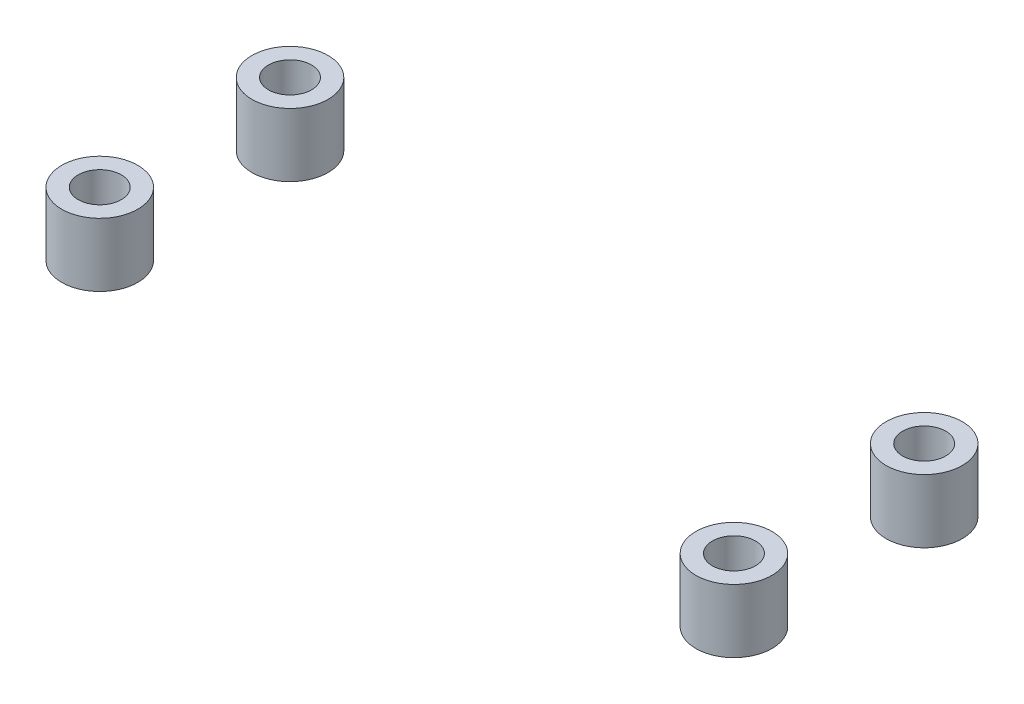
SolidWorks part; units mm, degrees
ref_plane "Front Plane" through (0, 0, 0) normal (0, 0, 1) x (1, 0, 0)
ref_plane "Top Plane" through (0, 0, 0) normal (0, 1, 0) x (1, 0, 0)
ref_plane "Right Plane" through (0, 0, 0) normal (1, 0, 0) x (0, 0, -1)
sketch "Sketch1" plane through (0, 0, 0) normal (0, 1, 0) x (1, 0, 0)
  line L0 (-15.6, 17.4701) -> (-13.6201, 19.45) construction
  line L1 (-13.6201, 19.45) -> (13.6201, 19.45) construction
  line L2 (-15.6, 17.4701) -> (-15.6, -19.45) construction
  line L3 (-15.6, -19.45) -> (15.6, -19.45) construction
  line L4 (15.6, 17.4701) -> (15.6, -19.45) construction
  line L5 (-14.7188, 18.3513) -> (15.6, -19.45) construction
  line L6 (-15.6, -19.45) -> (14.7188, 18.3513) construction
  line L7 (-13.6201, 19.45) -> (13.6201, 19.45) construction
  line L8 (13.6201, 19.45) -> (15.6, 17.4701) construction
  point P0 (0, 0)
  dimension "D1" = 31.2
  dimension "D2" = 38.9
  dimension "D3" = 45
  dimension "D4" = 2.8
  dimension "D5" = 2.8
  dimension "D6" = 19.45
  dimension "D7" = 15.6
sketch "Sketch2" plane through (0, 0, 0) normal (0, 1, 0) x (1, 0, 0)
  line L1 (-25, 7.5) -> (25, 7.5) construction
  line L2 (-25, 7.5) -> (-25, -7.5) construction
  line L3 (-25, -7.5) -> (25, -7.5) construction
  line L4 (25, 7.5) -> (25, -7.5) construction
  line L5 (-25, 7.5) -> (25, -7.5) construction
  line L6 (-25, -7.5) -> (25, 7.5) construction
  circle A0 centre (-25, 7.5) radius 1.7
  circle A1 centre (-25, -7.5) radius 1.7
  circle A2 centre (25, -7.5) radius 1.7
  circle A3 centre (25, 7.5) radius 1.7
  circle A4 centre (-25, 7.5) radius 3
  circle A5 centre (-25, -7.5) radius 3
  circle A6 centre (25, -7.5) radius 3
  circle A7 centre (25, 7.5) radius 3
  point P0 (0, 0)
  dimension "D3" = 3.4
  dimension "D4" = 6
  dimension "D1" = 50
  dimension "D2" = 15
extrude "Boss-Extrude1" add sketch "Sketch2" along normal blind 5
